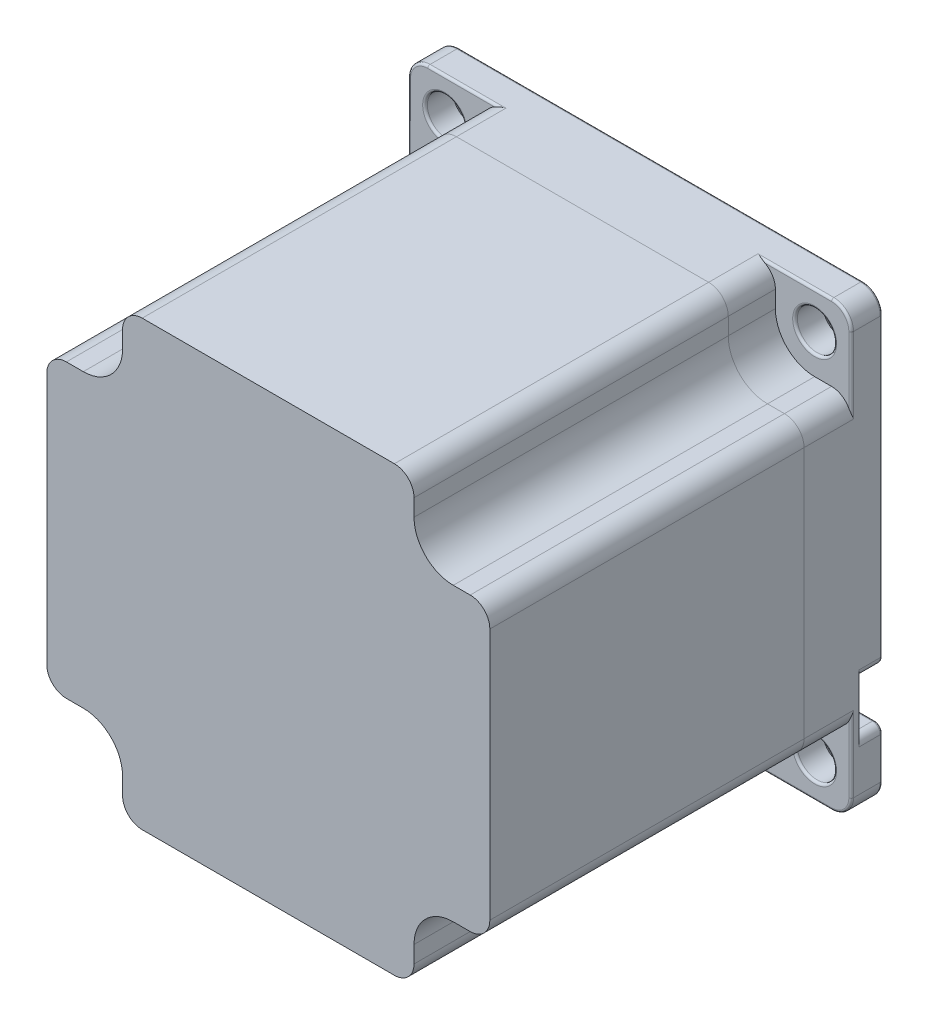
SolidWorks part; units mm, degrees
material "Alloy Steel"
ref_plane "Спереди" through (0, 0, 0) normal (0, 0, 1) x (1, 0, 0)
ref_plane "Сверху" through (0, 0, 0) normal (0, 1, 0) x (1, 0, 0)
ref_plane "Справа" through (0, 0, 0) normal (1, 0, 0) x (0, 0, -1)
sketch "Эскиз1" plane through (0, 0, 0) normal (0, 0, 1) x (1, 0, 0)
  line L1 (-28.2, -28.2) -> (28.2, -28.2)
  line L2 (-28.2, -28.2) -> (-28.2, 28.2)
  line L3 (-28.2, 28.2) -> (28.2, 28.2)
  line L4 (28.2, -28.2) -> (28.2, 28.2)
  line L5 (-28.2, -28.2) -> (28.2, 28.2) construction
  line L6 (-28.2, 28.2) -> (28.2, -28.2) construction
  point P0 (0, 0)
  dimension "D1" = 56.4
extrude "Бобышка-Вытянуть1" add sketch "Эскиз1" along normal blind 10
sketch "Эскиз2" plane through (0, 0, 10) normal (0, 0, 1) x (1, 0, 0)
  line L1 (-23.55, -23.55) -> (23.55, -23.55) construction
  line L2 (-23.55, -23.55) -> (-23.55, 23.55) construction
  line L3 (-23.55, 23.55) -> (23.55, 23.55) construction
  line L4 (23.55, -23.55) -> (23.55, 23.55) construction
  line L5 (-23.55, -23.55) -> (23.55, 23.55) construction
  line L6 (-23.55, 23.55) -> (23.55, -23.55) construction
  circle A0 centre (-23.55, 23.55) radius 2.5
  circle A1 centre (23.55, 23.55) radius 2.5
  circle A2 centre (23.55, -23.55) radius 2.5
  circle A3 centre (-23.55, -23.55) radius 2.5
  point P0 (0, 0)
  dimension "D1" = 5
  dimension "D2" = 47.1
extrude "Вырез-Вытянуть1" cut sketch "Эскиз2" against normal through all
sketch "Эскиз3" plane through (0, 0, 10) normal (0, 0, 1) x (1, 0, 0)
  line L0 (-18.55, 23.55) -> (-18.55, 28.2)
  line L1 (28.2, 28.2) -> (-28.2, 28.2) construction
  line L2 (-18.55, 28.2) -> (-28.2, 28.2)
  line L3 (-28.2, 28.2) -> (-28.2, 18.55)
  line L4 (-28.2, 28.2) -> (-28.2, -28.2) construction
  line L5 (-28.2, 18.55) -> (-23.55, 18.55)
  line L6 (18.55, 23.55) -> (18.55, 28.2)
  line L7 (18.55, 28.2) -> (28.2, 28.2)
  line L8 (28.2, 28.2) -> (28.2, 18.55)
  line L9 (28.2, -28.2) -> (28.2, 28.2) construction
  line L10 (28.2, 18.55) -> (23.55, 18.55)
  line L11 (18.55, -23.55) -> (18.55, -28.2)
  line L12 (-28.2, -28.2) -> (28.2, -28.2) construction
  line L13 (18.55, -28.2) -> (28.2, -28.2)
  line L14 (28.2, -28.2) -> (28.2, -18.55)
  line L15 (28.2, -18.55) -> (23.55, -18.55)
  line L16 (-23.55, -18.55) -> (-28.2, -18.55)
  line L17 (-28.2, -18.55) -> (-28.2, -28.2)
  line L18 (-28.2, -28.2) -> (-18.55, -28.2)
  line L19 (-18.55, -28.2) -> (-18.55, -23.55)
  arc A0 (-23.55, 18.55) -> (-18.55, 23.55) centre (-23.55, 23.55) ccw
  arc A1 (18.55, 23.55) -> (23.55, 18.55) centre (23.55, 23.55) ccw
  arc A2 (23.55, -18.55) -> (18.55, -23.55) centre (23.55, -23.55) ccw
  arc A3 (-18.55, -23.55) -> (-23.55, -18.55) centre (-23.55, -23.55) ccw
  dimension "D1" = 10
extrude "Вырез-Вытянуть2" cut sketch "Эскиз3" against normal blind 6
fillet "Скругление1" radius 2.5 12 edges at (28.2, -28.2, 2) (28.2, -18.55, 7) (18.55, -28.2, 7) (-18.55, -28.2, 7) (-28.2, -18.55, 7) (-28.2, -28.2, 2) (-28.2, 18.55, 7) (-18.55, 28.2, 7) (-28.2, 28.2, 2) (28.2, 18.55, 7) (18.55, 28.2, 7) (28.2, 28.2, 2)
sketch "Эскиз4" plane through (0, 0, 0) normal (0, 0, -1) x (-1, 0, 0)
  circle A0 centre (0, 0) radius 19.05
  dimension "D1" = 38.1
extrude "Бобышка-Вытянуть2" add sketch "Эскиз4" along normal blind 1.6
sketch "Эскиз5" plane through (0, 0, 0) normal (0, 0, -1) x (-1, 0, 0)
  circle A0 centre (0, 0) radius 3.175
  dimension "D1" = 6.35
extrude "Бобышка-Вытянуть3" add sketch "Эскиз5" along normal blind 20.6
sketch "Эскиз6" plane through (0, 0, -1.6) normal (0, 0, -1) x (-1, 0, 0)
  circle A0 centre (0, 0) radius 5.5
  circle A1 centre (0, 0) radius 3.175 construction
  circle A2 centre (0, 0) radius 3.175
  dimension "D1" = 11
extrude "Вырез-Вытянуть3" cut sketch "Эскиз6" against normal blind 2.5
chamfer "Фаска1" distance 0.5 angle 45 5 edges at (-3.175, 0, -20.6) (26.05, -23.55, 0) (-21.05, -23.55, 0) (-21.05, 23.55, 0) (26.05, 23.55, 0)
sketch "Эскиз7" plane through (0, 0, -20.6) normal (0, 0, -1) x (-1, 0, 0)
  circle A0 centre (0, 0) radius 1
  dimension "D1" = 2
extrude "Вырез-Вытянуть4" cut sketch "Эскиз7" against normal blind 3
sketch "Эскиз8" plane through (0, 0, 0) normal (0, 0, -1) x (-1, 0, 0)
  line L0 (-28.2, -16.2) -> (-25.45, -16.2) construction
  line L1 (-28.2, -25.7) -> (-28.2, 25.7) construction
  line L2 (-28.2, -12.95) -> (-25.45, -12.95)
  line L3 (-28.2, -19.45) -> (-25.45, -19.45)
  line L4 (25.7, -28.2) -> (-25.7, -28.2) construction
  arc A0 (-28.2, -12.95) -> (-28.2, -19.45) centre (-28.2, -16.2) ccw
  arc A1 (-25.45, -19.45) -> (-25.45, -12.95) centre (-25.45, -16.2) ccw
  point P4 (-26.825, -16.2)
  dimension "D1" = 3.25
  dimension "D2" = 6
  dimension "D3" = 12
extrude "Вырез-Вытянуть5" cut sketch "Эскиз8" against normal blind 3
fillet "Скругление2" radius 1 2 edges at (28.2, -19.45, 1.5) (28.2, -12.95, 1.5)
sketch "Эскиз9" plane through (0, 0, 3) normal (0, 0, -1) x (-1, 0, 0)
  circle A0 centre (-25.45, -16.2) radius 2.5
  dimension "D1" = 5
extrude "Бобышка-Вытянуть4" [suppressed] add sketch "Эскиз9" along normal blind 2 separate body
fillet "Скругление3" [suppressed] radius 1.5
fillet "Скругление4" [suppressed] radius 0.5
sketch "Эскиз10" [suppressed] plane through (0, 0, 1) normal (0, 0, -1) x (-1, 0, 0)
  line L0 (-25.05, -15.3) -> (-25.05, -14.2)
  line L1 (-25.85, -18.2) -> (-25.05, -18.2)
  line L2 (-25.85, -18.2) -> (-25.85, -17.1)
  line L3 (-25.85, -14.2) -> (-25.05, -14.2)
  line L4 (-25.05, -18.2) -> (-25.05, -17.1)
  line L5 (-25.85, -18.2) -> (-25.05, -14.2) construction
  line L6 (-25.85, -14.2) -> (-25.05, -18.2) construction
  line L7 (-27.45, -16.6) -> (-26.35, -16.6)
  line L8 (-27.45, -16.6) -> (-27.45, -15.8)
  line L9 (-27.45, -15.8) -> (-26.35, -15.8)
  line L10 (-23.45, -16.6) -> (-23.45, -15.8)
  line L11 (-27.45, -16.6) -> (-23.45, -15.8) construction
  line L12 (-27.45, -15.8) -> (-23.45, -16.6) construction
  line L13 (-24.55, -15.8) -> (-23.45, -15.8)
  line L14 (-25.85, -15.3) -> (-25.85, -14.2)
  line L15 (-24.55, -16.6) -> (-23.45, -16.6)
  arc A0 (-25.85, -17.1) -> (-26.35, -16.6) centre (-26.35, -17.1) ccw
  arc A1 (-25.05, -17.1) -> (-24.55, -16.6) centre (-24.55, -17.1) cw
  arc A2 (-25.05, -15.3) -> (-24.55, -15.8) centre (-24.55, -15.3) ccw
  arc A3 (-26.35, -15.8) -> (-25.85, -15.3) centre (-26.35, -15.3) ccw
  point P0 (-25.45, -16.2)
  point P6 (-25.45, -16.2)
  point P19 (-25.05, -16.6)
  point P22 (-25.05, -15.8)
  point P25 (-25.85, -15.8)
  dimension "D4" = 0.5
  dimension "D1" = 4
  dimension "D2" = 4
  dimension "D3" = 0.8
extrude "Вырез-Вытянуть6" [suppressed] cut sketch "Эскиз10" against normal blind 1.5 draft 13
fillet "Скругление5" [suppressed] radius 0.5
fillet "Скругление6" [suppressed] radius 0.2
ref_axis "Ось1" through (0, 0, 50) along (0, 0, -1)
pattern_circular "Круговой массив2" [suppressed] count 4 over 360 about axis through (0, 0, 50) along (0, 0, -1) of bodies 110
sketch "Эскиз11" plane through (0, 0, 10) normal (0, 0, 1) x (1, 0, 0)
  line L12 (23.55, -18.55) -> (25.7, -18.55)
  line L13 (28.2, -16.05) -> (28.2, 16.05)
  line L14 (25.7, 18.55) -> (23.55, 18.55)
  line L15 (18.55, 23.55) -> (18.55, 25.7)
  line L16 (16.05, 28.2) -> (-16.05, 28.2)
  line L17 (-18.55, 25.7) -> (-18.55, 23.55)
  line L18 (-23.55, 18.55) -> (-25.7, 18.55)
  line L19 (-28.2, 16.05) -> (-28.2, -16.05)
  line L20 (-25.7, -18.55) -> (-23.55, -18.55)
  line L21 (-18.55, -23.55) -> (-18.55, -25.7)
  line L22 (-16.05, -28.2) -> (16.05, -28.2)
  line L23 (18.55, -25.7) -> (18.55, -23.55)
  line L24 (23.55, -18.55) -> (25.7, -18.55)
  line L25 (28.2, -16.05) -> (28.2, 16.05)
  line L26 (25.7, 18.55) -> (23.55, 18.55)
  line L27 (18.55, 23.55) -> (18.55, 25.7)
  line L28 (16.05, 28.2) -> (-16.05, 28.2)
  line L29 (-18.55, 25.7) -> (-18.55, 23.55)
  line L30 (-23.55, 18.55) -> (-25.7, 18.55)
  line L31 (-28.2, 16.05) -> (-28.2, -16.05)
  line L32 (-25.7, -18.55) -> (-23.55, -18.55)
  line L33 (-18.55, -23.55) -> (-18.55, -25.7)
  line L34 (-16.05, -28.2) -> (16.05, -28.2)
  line L35 (18.55, -25.7) -> (18.55, -23.55)
  arc A12 (25.7, -18.55) -> (28.2, -16.05) centre (25.7, -16.05) ccw
  arc A13 (28.2, 16.05) -> (25.7, 18.55) centre (25.7, 16.05) ccw
  arc A14 (18.55, 23.55) -> (23.55, 18.55) centre (23.55, 23.55) ccw
  arc A15 (18.55, 25.7) -> (16.05, 28.2) centre (16.05, 25.7) ccw
  arc A16 (-16.05, 28.2) -> (-18.55, 25.7) centre (-16.05, 25.7) ccw
  arc A17 (-23.55, 18.55) -> (-18.55, 23.55) centre (-23.55, 23.55) ccw
  arc A18 (-25.7, 18.55) -> (-28.2, 16.05) centre (-25.7, 16.05) ccw
  arc A19 (-28.2, -16.05) -> (-25.7, -18.55) centre (-25.7, -16.05) ccw
  arc A20 (-18.55, -23.55) -> (-23.55, -18.55) centre (-23.55, -23.55) ccw
  arc A21 (-18.55, -25.7) -> (-16.05, -28.2) centre (-16.05, -25.7) ccw
  arc A22 (16.05, -28.2) -> (18.55, -25.7) centre (16.05, -25.7) ccw
  arc A23 (23.55, -18.55) -> (18.55, -23.55) centre (23.55, -23.55) ccw
  arc A24 (25.7, -18.55) -> (28.2, -16.05) centre (25.7, -16.05) ccw
  arc A25 (28.2, 16.05) -> (25.7, 18.55) centre (25.7, 16.05) ccw
  arc A26 (18.55, 23.55) -> (23.55, 18.55) centre (23.55, 23.55) ccw
  arc A27 (18.55, 25.7) -> (16.05, 28.2) centre (16.05, 25.7) ccw
  arc A28 (-16.05, 28.2) -> (-18.55, 25.7) centre (-16.05, 25.7) ccw
  arc A29 (-23.55, 18.55) -> (-18.55, 23.55) centre (-23.55, 23.55) ccw
  arc A30 (-25.7, 18.55) -> (-28.2, 16.05) centre (-25.7, 16.05) ccw
  arc A31 (-28.2, -16.05) -> (-25.7, -18.55) centre (-25.7, -16.05) ccw
  arc A32 (-18.55, -23.55) -> (-23.55, -18.55) centre (-23.55, -23.55) ccw
  arc A33 (-18.55, -25.7) -> (-16.05, -28.2) centre (-16.05, -25.7) ccw
  arc A34 (16.05, -28.2) -> (18.55, -25.7) centre (16.05, -25.7) ccw
  arc A35 (23.55, -18.55) -> (18.55, -23.55) centre (23.55, -23.55) ccw
  dimension "D1" = 0
extrude "Бобышка-Вытянуть5" add sketch "Эскиз11" along normal blind 54 separate body
sketch "Эскиз12" plane through (0, 0, 64) normal (0, 0, 1) x (1, 0, 0)
  line L12 (23.55, -18.55) -> (25.7, -18.55)
  line L13 (28.2, -16.05) -> (28.2, 16.05)
  line L14 (25.7, 18.55) -> (23.55, 18.55)
  line L15 (18.55, 23.55) -> (18.55, 25.7)
  line L16 (16.05, 28.2) -> (-16.05, 28.2)
  line L17 (-18.55, 25.7) -> (-18.55, 23.55)
  line L18 (-23.55, 18.55) -> (-25.7, 18.55)
  line L19 (-28.2, 16.05) -> (-28.2, -16.05)
  line L20 (-25.7, -18.55) -> (-23.55, -18.55)
  line L21 (-18.55, -23.55) -> (-18.55, -25.7)
  line L22 (-16.05, -28.2) -> (16.05, -28.2)
  line L23 (18.55, -25.7) -> (18.55, -23.55)
  line L24 (23.55, -18.55) -> (25.7, -18.55)
  line L25 (28.2, -16.05) -> (28.2, 16.05)
  line L26 (25.7, 18.55) -> (23.55, 18.55)
  line L27 (18.55, 23.55) -> (18.55, 25.7)
  line L28 (16.05, 28.2) -> (-16.05, 28.2)
  line L29 (-18.55, 25.7) -> (-18.55, 23.55)
  line L30 (-23.55, 18.55) -> (-25.7, 18.55)
  line L31 (-28.2, 16.05) -> (-28.2, -16.05)
  line L32 (-25.7, -18.55) -> (-23.55, -18.55)
  line L33 (-18.55, -23.55) -> (-18.55, -25.7)
  line L34 (-16.05, -28.2) -> (16.05, -28.2)
  line L35 (18.55, -25.7) -> (18.55, -23.55)
  arc A12 (23.55, -18.55) -> (18.55, -23.55) centre (23.55, -23.55) ccw
  arc A13 (25.7, -18.55) -> (28.2, -16.05) centre (25.7, -16.05) ccw
  arc A14 (28.2, 16.05) -> (25.7, 18.55) centre (25.7, 16.05) ccw
  arc A15 (18.55, 23.55) -> (23.55, 18.55) centre (23.55, 23.55) ccw
  arc A16 (18.55, 25.7) -> (16.05, 28.2) centre (16.05, 25.7) ccw
  arc A17 (-16.05, 28.2) -> (-18.55, 25.7) centre (-16.05, 25.7) ccw
  arc A18 (-23.55, 18.55) -> (-18.55, 23.55) centre (-23.55, 23.55) ccw
  arc A19 (-25.7, 18.55) -> (-28.2, 16.05) centre (-25.7, 16.05) ccw
  arc A20 (-28.2, -16.05) -> (-25.7, -18.55) centre (-25.7, -16.05) ccw
  arc A21 (-18.55, -23.55) -> (-23.55, -18.55) centre (-23.55, -23.55) ccw
  arc A22 (-18.55, -25.7) -> (-16.05, -28.2) centre (-16.05, -25.7) ccw
  arc A23 (16.05, -28.2) -> (18.55, -25.7) centre (16.05, -25.7) ccw
  arc A24 (23.55, -18.55) -> (18.55, -23.55) centre (23.55, -23.55) ccw
  arc A25 (25.7, -18.55) -> (28.2, -16.05) centre (25.7, -16.05) ccw
  arc A26 (28.2, 16.05) -> (25.7, 18.55) centre (25.7, 16.05) ccw
  arc A27 (18.55, 23.55) -> (23.55, 18.55) centre (23.55, 23.55) ccw
  arc A28 (18.55, 25.7) -> (16.05, 28.2) centre (16.05, 25.7) ccw
  arc A29 (-16.05, 28.2) -> (-18.55, 25.7) centre (-16.05, 25.7) ccw
  arc A30 (-23.55, 18.55) -> (-18.55, 23.55) centre (-23.55, 23.55) ccw
  arc A31 (-25.7, 18.55) -> (-28.2, 16.05) centre (-25.7, 16.05) ccw
  arc A32 (-28.2, -16.05) -> (-25.7, -18.55) centre (-25.7, -16.05) ccw
  arc A33 (-18.55, -23.55) -> (-23.55, -18.55) centre (-23.55, -23.55) ccw
  arc A34 (-18.55, -25.7) -> (-16.05, -28.2) centre (-16.05, -25.7) ccw
  arc A35 (16.05, -28.2) -> (18.55, -25.7) centre (16.05, -25.7) ccw
  dimension "D1" = 0
extrude "Бобышка-Вытянуть6" add sketch "Эскиз12" along normal blind 11 separate body
fillet "Скругление7" radius 0.5 24 edges at (27.4678, -17.8178, 75) (24.625, -18.55, 75) (20.0145, -20.0145, 75) (18.55, -24.625, 75) (17.8178, -27.4678, 75) (0, -28.2, 75) (-17.8178, -27.4678, 75) (-18.55, -24.625, 75) (-20.0145, -20.0145, 75) (-24.625, -18.55, 75) (-27.4678, -17.8178, 75) (-28.2, 0, 75) (-27.4678, 17.8178, 75) (-24.625, 18.55, 75) (-20.0145, 20.0145, 75) (-18.55, 24.625, 75) (-17.8178, 27.4678, 75) (0, 28.2, 75) (17.8178, 27.4678, 75) (18.55, 24.625, 75) (20.0145, 20.0145, 75) (24.625, 18.55, 75) (27.4678, 17.8178, 75) (28.2, 0, 75)
sketch "Эскиз13" [suppressed] plane through (0, 0, 75) normal (0, 0, 1) x (1, 0, 0)
  circle A0 centre (16.2, 25.45) radius 1.25
  circle A1 centre (-25.4912, 16.2) radius 1.25
  circle A2 centre (-16.2, -25.45) radius 1.25
  circle A3 centre (25.45, -16.2) radius 1.25
  dimension "D1" = 2.5
extrude "Вырез-Вытянуть7" [suppressed] cut sketch "Эскиз13" against normal blind 2
chamfer "Фаска2" [suppressed] distance 0.2 angle 45
sketch "Эскиз14" plane through (0, 0, 75) normal (0, 0, 1) x (1, 0, 0)
  circle A0 centre (0, 0) radius 5.5
  dimension "D1" = 11
extrude "Вырез-Вытянуть8" cut sketch "Эскиз14" against normal blind 4
sketch "Эскиз15" plane through (0, 0, 71) normal (0, 0, 1) x (1, 0, 0)
  circle A0 centre (0, 0) radius 3.25
  dimension "D1" = 6.5
extrude "Бобышка-Вытянуть7" add sketch "Эскиз15" along normal blind 1
sketch "Эскиз16" plane through (0, 0, 72) normal (0, 0, 1) x (1, 0, 0)
  circle A0 centre (0, 0) radius 1
  dimension "D1" = 2
extrude "Вырез-Вытянуть9" cut sketch "Эскиз16" against normal blind 3
chamfer "Фаска3" distance 1 angle 45 1 edges at (3.25, 0, 71)
fillet "Скругление8" radius 0.5 1 edges at (5.5, 0, 75)
fillet "Скругление9" radius 0.3 33 edges at (-20.875, 28.2, 4) (-27.4678, 27.4678, 4) (-28.2, -20.875, 4) (-27.4678, -27.4678, 4) (20.875, -28.2, 4) (27.4678, -27.4678, 4) (28.2, 20.875, 4) (27.4678, 27.4678, 4) (0, 28.2, 0) (27.4678, 27.4678, 0) (28.2, 6.875, 0) (27.9071, -12.6571, 0) (26.325, -12.95, 0) (22.2, -16.2, 0) (26.325, -19.45, 0) (27.9071, -19.7429, 0) (28.2, -23.075, 0) (27.4678, -27.4678, 0) (0, -28.2, 0) (-27.4678, -27.4678, 0) (-28.2, 0, 0) (-27.4678, 27.4678, 0) (26.05, 23.55, 4) (-21.05, -23.55, 4) (-21.05, 23.55, 4) (-28.2, 20.875, 4) (-20.875, -28.2, 4) (28.2, -20.875, 4) (20.875, 28.2, 4) (26.05, -23.55, 4) (-19.05, 0, 0) (-19.05, 0, -1.6) (-5.5, 0, -1.6)
sketch "Эскиз17" plane through (28.2, 0, 0) normal (1, 0, 0) x (0, 0, -1)
  line L0 (-68.4, -6) -> (-64.4, -6)
  line L1 (-64.4, -6) -> (-64.4, 6)
  line L2 (-64.4, 6) -> (-68.4, 6)
  line L3 (-64, -16.05) -> (-64, 16.05) construction
  arc A0 (-68.4, -6) -> (-68.4, 6) centre (-68.4, 0) cw
  circle A1 centre (-68.4, 0) radius 2.5
  dimension "D2" = 4
  dimension "D4" = 5
  dimension "D1" = 12
  dimension "D3" = 0.4
extrude "Бобышка-Вытянуть8" [suppressed] add sketch "Эскиз17" along normal blind 2 and the other way blind 0.5 separate body
combine bodies "Combine1" [suppressed] operation type add bodies to combine 112 119 110 120 114
sketch "Sketch1" plane through (0, -28.2, 0) normal (0, -1, 0) x (1, 0, 0)
  line L0 (0, -20.6) -> (0, -1.6) construction
  line L1 (-1, -20.6) -> (1, -20.6) construction
  line L2 (-18.75, -1.6) -> (18.75, -1.6) construction
sketch "Sketch2" plane through (0, -28.2, 0) normal (0, -1, 0) x (1, 0, 0)
  line L0 (0, 0) -> (0, 50) construction
  line L2 (36.1825, 50) -> (-37.2626, 50)
  line L3 (36.1825, 50) -> (36.1825, 81.1514)
  line L4 (36.1825, 81.1514) -> (-37.2626, 81.1514)
  line L5 (-37.2626, 50) -> (-37.2626, 81.1514)
  dimension "D1" = 50
extrude "Cut-Extrude1" cut sketch "Sketch2" against normal through all
